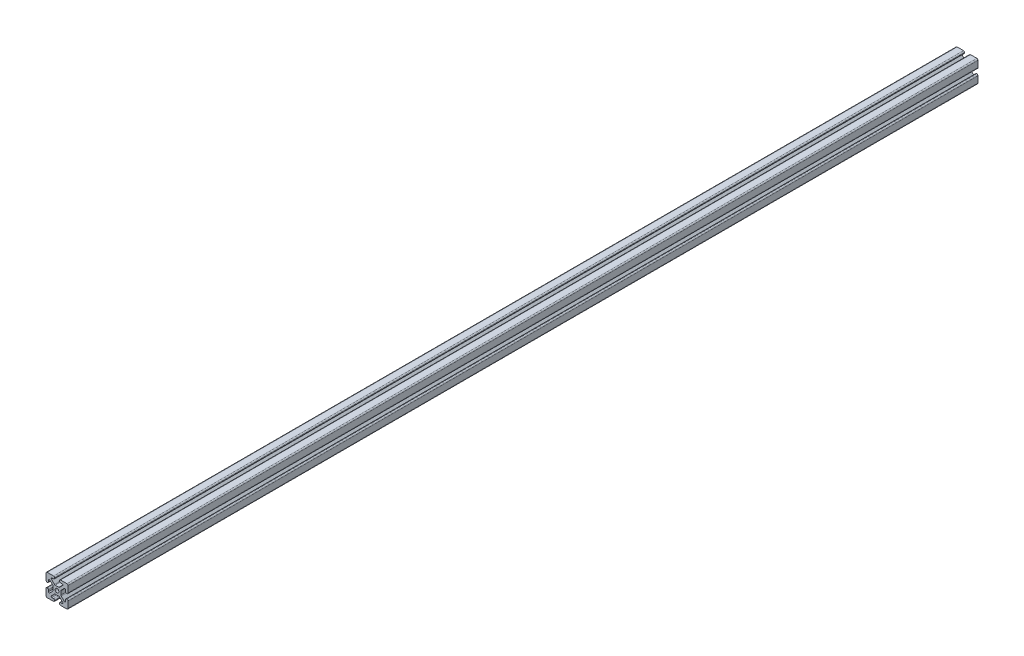
SolidWorks part; units mm, degrees
material "1060 Alloy"
ref_plane "Front" through (0, 0, 0) normal (0, 0, 1) x (1, 0, 0)
ref_plane "Top" through (0, 0, 0) normal (0, 1, 0) x (1, 0, 0)
ref_plane "Right" through (0, 0, 0) normal (1, 0, 0) x (0, 0, -1)
sketch "Sketch1" plane through (0, 0, 0) normal (0, 0, 1) x (1, 0, 0)
  line L0 (0, 0) -> (6.7437, 0)
  line L1 (6.7437, 0) -> (6.7437, 6.7437)
  line L2 (6.7437, 6.7437) -> (-6.7437, 6.7437)
  line L3 (-6.7437, 6.7437) -> (-6.7437, -6.7437)
  line L4 (-6.7437, -6.7437) -> (6.7437, -6.7437)
  line L5 (6.7437, -6.7437) -> (6.7437, 0)
  line L6 (0, 6.7437) -> (4.064, 6.7437)
  line L7 (4.064, 6.7437) -> (4.064, 25.2303)
  line L8 (0, 6.7437) -> (-4.064, 6.7437)
  line L9 (-4.064, 6.7437) -> (-4.064, 25.2303)
  line L10 (0, 0) -> (0, 19.05)
  line L11 (0, 19.05) -> (19.05, 19.05)
  line L12 (19.05, 19.05) -> (19.05, -19.05)
  line L13 (19.05, -19.05) -> (-19.05, -19.05)
  line L14 (-19.05, -19.05) -> (-19.05, 19.05)
  line L15 (-19.05, 19.05) -> (0, 19.05)
  line L16 (4.064, 6.7437) -> (4.064, -19.05)
  line L17 (-4.064, 6.7437) -> (-4.064, -19.05)
  line L18 (6.7437, 0) -> (6.7437, -4.064)
  line L19 (6.7437, -4.064) -> (19.05, -4.064)
  line L20 (6.7437, 0) -> (6.7437, 4.064)
  line L21 (6.7437, 4.064) -> (19.05, 4.064)
  line L22 (6.7437, 4.064) -> (-19.05, 4.064)
  line L23 (6.7437, -4.064) -> (-19.05, -4.064)
  line L24 (-19.05, 19.05) -> (19.05, -19.05) construction
  line L25 (19.05, 19.05) -> (-19.05, -19.05) construction
  line L26 (-20.4868, 17.6132) -> (17.6132, -20.4868)
  line L27 (17.6132, 20.4868) -> (-20.4868, -17.6132)
  line L28 (-17.6132, 20.4868) -> (20.4868, -17.6132)
  line L29 (20.4868, 17.6132) -> (-17.6132, -20.4868)
  line L30 (-6.7437, -6.7437) -> (-6.7437, -14.7447)
  line L31 (-6.7437, -14.7447) -> (-19.05, -14.7447)
  line L32 (-6.7437, -14.7447) -> (19.05, -14.7447)
  line L33 (-6.7437, 6.7437) -> (-6.7437, 14.7447)
  line L34 (-6.7437, 14.7447) -> (19.05, 14.7447)
  line L35 (-6.7437, 14.7447) -> (-19.05, 14.7447)
  line L36 (-6.7437, 6.7437) -> (-14.7447, 6.7437)
  line L37 (-14.7447, 6.7437) -> (-14.7447, 19.05)
  line L38 (-14.7447, 6.7437) -> (-14.7447, -19.05)
  line L39 (6.7437, 6.7437) -> (14.7447, 6.7437)
  line L40 (14.7447, 6.7437) -> (14.7447, 19.05)
  line L41 (14.7447, 6.7437) -> (14.7447, -19.05)
  circle A0 centre (0, 0) radius 3.3274
  dimension "D1" = 2.032
  dimension "D2" = 2.032
extrude "Boss-Extrude1" add sketch "Sketch1" along normal blind 1574.8 contours L35 L26 L14 | L28 L37 L15 | L40 L27 L11 | L29 L34 L12 | L32 L28 L12 | L26 L41 L13 | L32 L41 L26 L13 L12 L28 | L19 L41 L28 L32 L12 | L28 L41 L32 | L41 L32 L26 | L41 L26 L32 L16 L13 | L40 L41 L21 L12 L34 L29 | L40 L29 L34 | L40 L34 L29 L12 L11 L27 | L27 L40 L11 L7 L34 | L34 L40 L27 | L37 L28 L35 L34 L9 L15 | L37 L35 L28 | L35 L37 L28 L15 L14 L26 | L26 L37 L35 | L38 L37 L26 L35 L14 L22 | L38 L23 L14 L31 L27 | L38 L27 L31 | L27 L31 L14 | L38 L31 L27 L14 L13 L29 | L38 L29 L13 | L31 L38 L29 | L29 L38 L13 L17 L32 L31 | L27 L38 L31 L29 L30 L3 L23 | L4 L30 L29 L17 | L17 L23 L3 L4 | L41 L28 L19 L5 L4 L16 L26 L32 | L29 L40 L34 L27 L7 L2 L39 | L39 L1 L21 L29 | L37 L26 L36 L33 L28 L35 | L33 L2 L9 L28 | L3 L36 L26 L22 | L22 L17 L2 L3 | L3 L26 L17 L22 | L27 L17 L26 L3 | A0 L28 L22 L17 L26 | L28 L8 L17 L22 | L2 L28 L22 L10 | A0 L10 L22 L28 | A0 L27 L22 L10 | L27 L6 L10 L22 | L2 L27 L22 L16 | L22 L1 L2 L16 | L29 L20 L22 L16 | L1 L29 L16 L0 | A0 L29 L16 L22 L27 | A0 L0 L16 L29 | A0 L28 L16 L0 | L16 L28 L18 L0 | L28 L16 L23 L5 | A0 L26 L23 L16 L28 | L5 L23 L16 L4 | L23 L26 L4 L16 | L23 L29 L4 L26 | A0 L29 L23 L26 | A0 L27 L17 L23 L29 | L17 L27 L3 L23 | A0 L26 L17 L27 | L4 L26 L16 | L28 L5 L19 | L29 L21 L20 | L7 L27 L2 | L28 L9 L8 | L22 L26 L3 | L3 L27 L23 | L29 L4 L17 | L29 L23 L17 L4 region at (3.7477, 0.4378, 0) region at (3.7477, -0.4378, 0) region at (2.8373, -2.8373, 0) region at (2.8373, 2.8373, 0) region at (-0.4378, 3.7477, 0) region at (0.4378, 3.7477, 0) region at (-2.8373, 2.8373, 0) region at (5.6404, 1.3833, 0) region at (5.6404, -1.3833, 0) region at (5.0137, -3.102, 0) region at (0, -3.7477, 0) region at (5.0137, 3.102, 0) region at (-2.8373, -2.8373, 0) region at (-1.3833, 5.6404, 0) region at (1.3833, 5.6404, 0) region at (3.102, 5.0137, 0) region at (-3.7477, 0, 0) region at (-3.102, 5.0137, 0) region at (5.4039, -5.4039, 0) region at (3.102, -5.0137, 0) region at (6.8084, -3.9993, 0) region at (0, -5.6404, 0) region at (5.4039, 5.4039, 0) region at (6.8084, 3.9993, 0) region at (-3.102, -5.0137, 0) region at (3.9993, 6.8084, 0) region at (-5.0137, 3.102, 0) region at (-5.6404, 0, 0) region at (-5.0137, -3.102, 0) region at (-5.4039, 5.4038, 0) region at (-3.9993, 6.8084, 0) region at (3.9993, -6.8084, 0) region at (10.0296, -10.0296, 0) region at (10.2579, 10.4457, 0) region at (7.7057, 5.794, 0) region at (-5.4038, -5.4039, 0) region at (-3.9993, -6.8084, 0) region at (-6.8084, 3.9993, 0) region at (-6.8084, -3.9993, 0) region at (-5.794, 7.7057, 0) region at (-7.7057, 5.794, 0) region at (17.0152, -8.972, 0) region at (15.7026, -13.7868, 0) region at (17.0152, 8.972, 0) region at (-5.794, -7.7057, 0) region at (-10.4457, -10.2579, 0) region at (-8.972, 17.0152, 0) region at (8.972, 17.0152, 0) region at (13.7868, 15.7026, 0) region at (-10.7442, 10.7442, 0) region at (8.972, -17.0152, 0) region at (13.7868, -15.7026, 0) region at (18.5728, -15.2219, 0) region at (16.8973, -16.8973, 0) region at (15.7026, 13.7868, 0) region at (-8.972, -17.0152, 0) region at (15.2219, 18.5728, 0) region at (16.8973, 16.8973, 0) region at (-17.0152, 8.972, 0) region at (-17.0152, -8.972, 0)
fillet "Fillet2" radius 2.032 8 edges at (-6.7437, -3.87, 787.4) (-6.7437, 3.87, 787.4) (-3.87, 6.7437, 787.4) (3.87, 6.7437, 787.4) (6.7437, 3.87, 787.4) (6.7437, -3.87, 787.4) (-3.87, -6.7437, 787.4) (3.87, -6.7437, 787.4)
fillet "Fillet3" radius 2.032 20 edges at (-19.05, -19.05, 787.4) (19.05, -19.05, 787.4) (19.05, 19.05, 787.4) (4.064, 14.7447, 787.4) (4.064, 19.05, 787.4) (-19.05, 19.05, 787.4) (-14.7447, -4.064, 787.4) (-19.05, -4.064, 787.4) (-19.05, 4.064, 787.4) (-14.7447, 4.064, 787.4) (-4.064, 14.7447, 787.4) (-4.064, 19.05, 787.4) (19.05, 4.064, 787.4) (14.7447, 4.064, 787.4) (-4.064, -19.05, 787.4) (-4.064, -14.7447, 787.4) (4.064, -19.05, 787.4) (4.064, -14.7447, 787.4) (14.7447, -4.064, 787.4) (19.05, -4.064, 787.4)
fillet "Fillet4" radius 1.27 8 edges at (-14.7447, 11.871, 787.4) (-11.871, 14.7447, 787.4) (11.871, 14.7447, 787.4) (14.7447, 11.871, 787.4) (14.7447, -11.871, 787.4) (11.871, -14.7447, 787.4) (-11.871, -14.7447, 787.4) (-14.7447, -11.871, 787.4)
